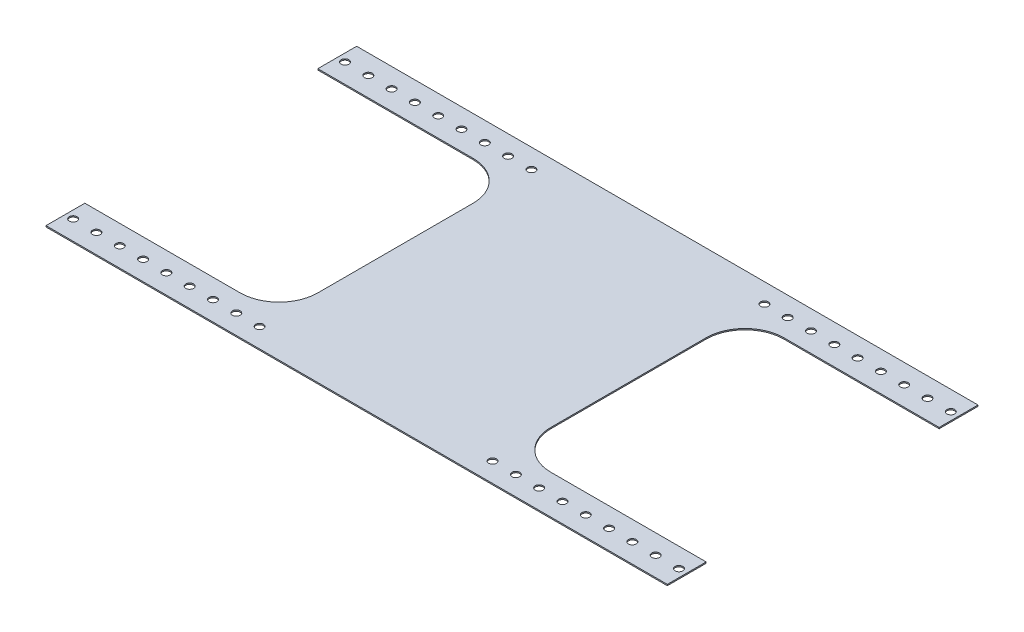
SolidWorks part; units mm, degrees
ref_plane "Front Plane" through (0, 0, 0) normal (0, 0, 1) x (1, 0, 0)
ref_plane "Top Plane" through (0, 0, 0) normal (0, 1, 0) x (1, 0, 0)
ref_plane "Right Plane" through (0, 0, 0) normal (1, 0, 0) x (0, 0, -1)
sketch "Sketch3" plane through (0, 0, 0) normal (0, 1, 0) x (1, 0, 0)
  line L0 (-200, 100) -> (200, 100)
  line L1 (-200, 100) -> (-200, 75)
  line L2 (-200, 75) -> (-100, 75)
  line L3 (-75, 50) -> (-75, -50)
  line L4 (0, 0) -> (-261.7187, 0) construction
  line L5 (0, 0) -> (0, 124.0234) construction
  line L6 (75, 50) -> (75, -50)
  line L7 (200, 75) -> (100, 75)
  line L8 (200, 100) -> (200, 75)
  line L9 (200, -100) -> (200, -75)
  line L10 (200, -75) -> (100, -75)
  line L11 (-200, -75) -> (-100, -75)
  line L12 (-200, -100) -> (-200, -75)
  line L13 (-200, -100) -> (200, -100)
  arc A0 (75, 50) -> (100, 75) centre (100, 50) cw
  arc A1 (100, -75) -> (75, -50) centre (100, -50) cw
  arc A2 (-100, -75) -> (-75, -50) centre (-100, -50) ccw
  arc A3 (-100, 75) -> (-75, 50) centre (-100, 50) cw
  point P13 (0, 100)
  point P16 (75, 0)
  point P17 (-75, 0)
  point P21 (75, 75)
  point P24 (75, -75)
  point P27 (-75, -75)
  point P30 (-75, 75)
  dimension "D5" = 25
  dimension "D1" = 25
  dimension "D2" = 125
  dimension "D3" = 200
  dimension "D4" = 150
extrude "Sheet" add sketch "Sketch3" along normal blind 0.7937
sketch "Sketch4" plane through (0, 0.7937, 0) normal (0, 1, 0) x (1, 0, 0)
  line L0 (-200, 87.5) -> (-75, 87.5) construction
  line L1 (-200, 100) -> (-200, 75) construction
  line L2 (-75, 50) -> (-75, -50) construction
  circle A0 centre (-195, 87.5) radius 2.5
  circle A1 centre (-180, 87.5) radius 2.5
  circle A2 centre (-165, 87.5) radius 2.5
  circle A3 centre (-150, 87.5) radius 2.5
  circle A4 centre (-135, 87.5) radius 2.5
  circle A10 centre (-120, 87.5) radius 2.5
  circle A11 centre (-105, 87.5) radius 2.5
  circle A12 centre (-90, 87.5) radius 2.5
  circle A13 centre (-75, 87.5) radius 2.5
  dimension "D1" = 5
  dimension "D2" = 5
  dimension "D4" = 15
  dimension "D3" = 9
extrude "MountHoles" cut sketch "Sketch4" against normal through all
mirror "Mirror3" about plane through (0, 0, 0) normal (0, 0, 1) of "MountHoles"
mirror "Mirror4" about plane through (0, 0, 0) normal (1, 0, 0) of "Mirror3"
